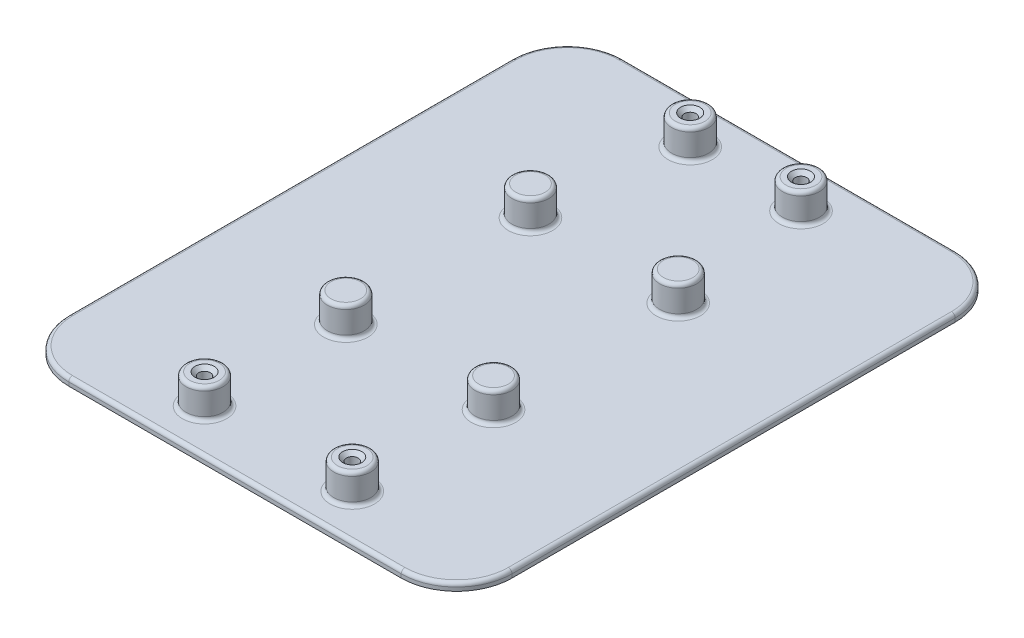
SolidWorks part; units mm, degrees
ref_plane "Front Plane" through (0, 0, 0) normal (0, 0, 1) x (1, 0, 0)
ref_plane "Top Plane" through (0, 0, 0) normal (0, 1, 0) x (1, 0, 0)
ref_plane "Right Plane" through (0, 0, 0) normal (1, 0, 0) x (0, 0, -1)
sketch "Sketch1" plane through (0, 0, 0) normal (0, 1, 0) x (1, 0, 0)
  line L1 (15, 0) -> (105, 0)
  line L2 (0, 15) -> (0, 135)
  line L3 (15, 150) -> (105, 150)
  line L4 (120, 15) -> (120, 135)
  arc A0 (15, 0) -> (0, 15) centre (15, 15) cw
  arc A1 (105, 0) -> (120, 15) centre (105, 15) ccw
  arc A2 (105, 150) -> (120, 135) centre (105, 135) cw
  arc A3 (0, 135) -> (15, 150) centre (15, 135) cw
  point P7 (0, 0)
  point P12 (120, 150)
  point P15 (0, 150)
  dimension "D3" = 15
  dimension "D1" = 150
  dimension "D2" = 120
extrude "Boss-Extrude1" add sketch "Sketch1" along normal blind 2
sketch "Sketch2" plane through (0, 2, 0) normal (0, 1, 0) x (1, 0, 0)
  line L0 (60, 0) -> (60, 150) construction
  line L1 (15, 0) -> (105, 0) construction
  line L2 (105, 150) -> (15, 150) construction
  line L3 (120, 75) -> (0, 75) construction
  line L4 (120, 15) -> (120, 135) construction
  line L5 (0, 135) -> (0, 15) construction
  circle A4 centre (45, 138.25) radius 5
  circle A5 centre (75, 138.25) radius 5
  circle A6 centre (40, 11.75) radius 5
  circle A7 centre (80, 11.75) radius 5
  circle A8 centre (40, 50) radius 5
  circle A9 centre (80, 50) radius 5
  circle A10 centre (40, 100) radius 5
  circle A11 centre (80, 100) radius 5
  point P13 (0, 0)
  point P17 (36.1808, 46.773)
  point P32 (0, 0)
  point P33 (0, 0)
  dimension "D2" = 30
  dimension "D4" = 126.5
  dimension "D6" = 40
  dimension "D8" = 10
  dimension "D9" = 10
  dimension "D12" = 20
  dimension "D13" = 25
  dimension "D3" = 15
  dimension "D5" = 63.25
  dimension "D7" = 20
  dimension "D10" = 40
  dimension "D11" = 50
extrude "Boss-Extrude2" add sketch "Sketch2" along normal blind 8
sketch "Sketch3" plane through (0, 10, 0) normal (0, 1, 0) x (1, 0, 0)
  circle A0 centre (45, 138.25) radius 1.5875
  circle A1 centre (75, 138.25) radius 1.5875
  circle A2 centre (40, 11.75) radius 1.5875
  circle A3 centre (80, 11.75) radius 1.5875
  dimension "D1" = 3.175
extrude "Cut-Extrude1" cut sketch "Sketch3" against normal blind 5
fillet "Fillet1" radius 1 24 edges at (0, 2, -75) (4.3934, 2, -145.6066) (60, 2, -150) (115.6066, 2, -145.6066) (120, 2, -75) (115.6066, 2, -4.3934) (60, 2, 0) (75, 10, -133.25) (45, 10, -133.25) (80, 10, -6.75) (40, 10, -6.75) (4.3934, 2, -4.3934) (80, 2, -16.75) (40, 2, -16.75) (75, 2, -143.25) (45, 2, -143.25) (80, 10, -95) (40, 10, -45) (80, 10, -45) (40, 10, -95) (80, 2, -55) (40, 2, -105) (40, 2, -55) (80, 2, -105)
chamfer "Chamfer1" distance 1 angle 45 4 edges at (80, 10, -10.1625) (40, 10, -10.1625) (75, 10, -136.6625) (45, 10, -136.6625)
